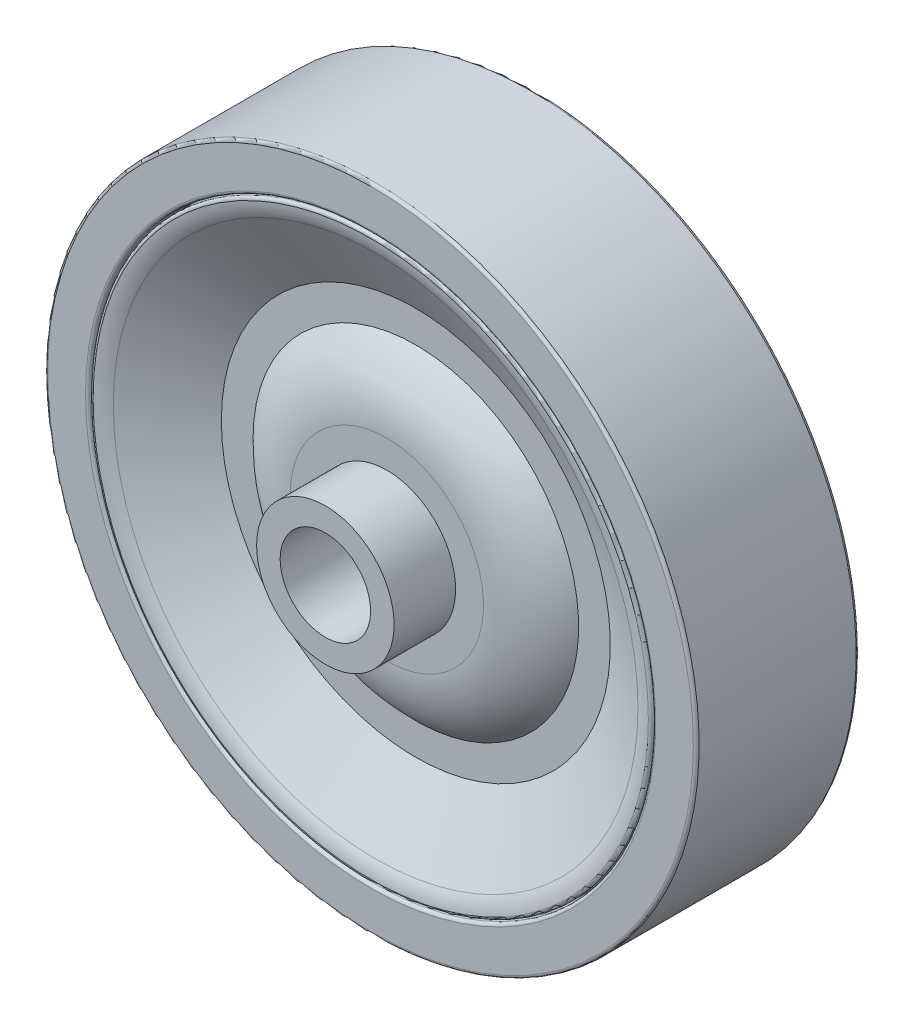
SolidWorks part; units mm, degrees
note: '?' marks a value the reader was unsure of.
other "Rubber Wheel"
other "Steel Bearing/Hubs" parameters "D2"=1.8939, "D8"=1.5854, "D1"=62.9296, "Dia"=41.529, "D3"=48.1831, "D4"=10.6508, "D5"=4.6621, "D6"=14.4946, "D7"=23.9615, "Bore Dia"=7.9375, "Hub Lg"=22.225, "Wheel Wd"=14.2875, "Wheel Dia"=57.15, "D9"=2.6319, "D10"=2.6319
material "POLYURETHANE (11671)"
ref_plane "Front" through (0, 0, 0) normal (0, 0, 1) x (1, 0, 0)
ref_plane "Top" through (0, 0, 0) normal (0, 1, 0) x (1, 0, 0)
ref_plane "Right" through (0, 0, 0) normal (1, 0, 0) x (0, 0, -1)
sketch "Sketch1" plane through (0, 0, 0) normal (1, 0, 0) x (0, 0, -1)
  line L0 (0, 28.575) -> (7.1437, 28.575)
  line L1 (0, 28.575) -> (0, 3.9688)
  line L2 (0, 3.9688) -> (11.1125, 3.9688)
  line L3 (11.1125, 3.9688) -> (11.1125, 6.0325)
  line L4 (11.1125, 6.0325) -> (5.715, 6.0325)
  line L5 (11.1125, 6.0325) -> (11.1125, -6.0325) construction
  line L6 (11.1125, 3.9688) -> (11.1125, -3.9688) construction
  line L7 (3.175, 17.0656) -> (6.7008, 23.0204)
  line L8 (0, 28.575) -> (0, -28.575) construction
  line L9 (11.1125, 0) -> (-11.1125, 0) construction
  line L10 (7.1437, 28.575) -> (-7.1437, 28.575) construction
  line L11 (5.715, 8.476) -> (5.715, 6.0325)
  line L12 (3.175, 14.2875) -> (3.175, 17.0656)
  line L13 (7.1437, 28.575) -> (7.1437, 24.765)
  line L14 (7.1437, 24.765) -> (4.6037, 24.765)
  line L15 (4.6037, 24.765) -> (4.6037, 24.638)
  line L16 (4.6037, 24.638) -> (7.1437, 24.638)
  line L19 (5.715, 6.0325) -> (-5.715, 6.0325) construction
  line L20 (3.175, 15.6766) -> (-3.175, 15.6766) construction
  arc A0 (7.1437, 24.638) -> (6.7008, 23.0204) centre (3.9688, 24.638) cw
  arc A2 (3.175, 14.2875) -> (5.715, 8.476) centre (-2.2034, 8.476) cw
  point P27 (0, 6.0325)
  point P31 (0, 15.6766)
  dimension "D8" = 3.175
  dimension "D1" = 12.065
  dimension "D3" = 11.43
  dimension "D4" = 6.35
  dimension "D5" = 14.2875
  dimension "D6" = 2.7781
  dimension "D7" = 2.4435
  dimension "D2" = 3.81
  dimension "D9" = 0.127
  dimension "D10" = 2.54
revolve "Revolve1" add sketch "Sketch1" angle 360 mid plane about L9
fillet "Fillet1" radius 0.254 3 edges at (-28.575, 0, -7.1437) (-24.765, 0, -7.1437) (-24.638, 0, -7.1437)
mirror "Mirror1" about plane through (0, 0, 0) normal (0, 0, 1) of bodies 109
sketch "Sketch2" plane through (0, 0, 7.1437) normal (0, 0, 1) x (1, 0, 0)
  circle A0 centre (0, 0) radius 24.638 construction
  circle A1 centre (0, 0) radius 24.765 construction
  circle A2 centre (0, 0) radius 24.638
  circle A3 centre (0, 0) radius 24.765
extrude "Cut-Extrude1" cut sketch "Sketch2" against normal through all both and the other way through all contours A3 A2
ref_axis "Center Axis 1" through (0, 0, 11.1125) along (0, 0, -1)?
equation "\"D1@Sketch1\" = \"Bore Dia@Sketch1\" * 1.52"
